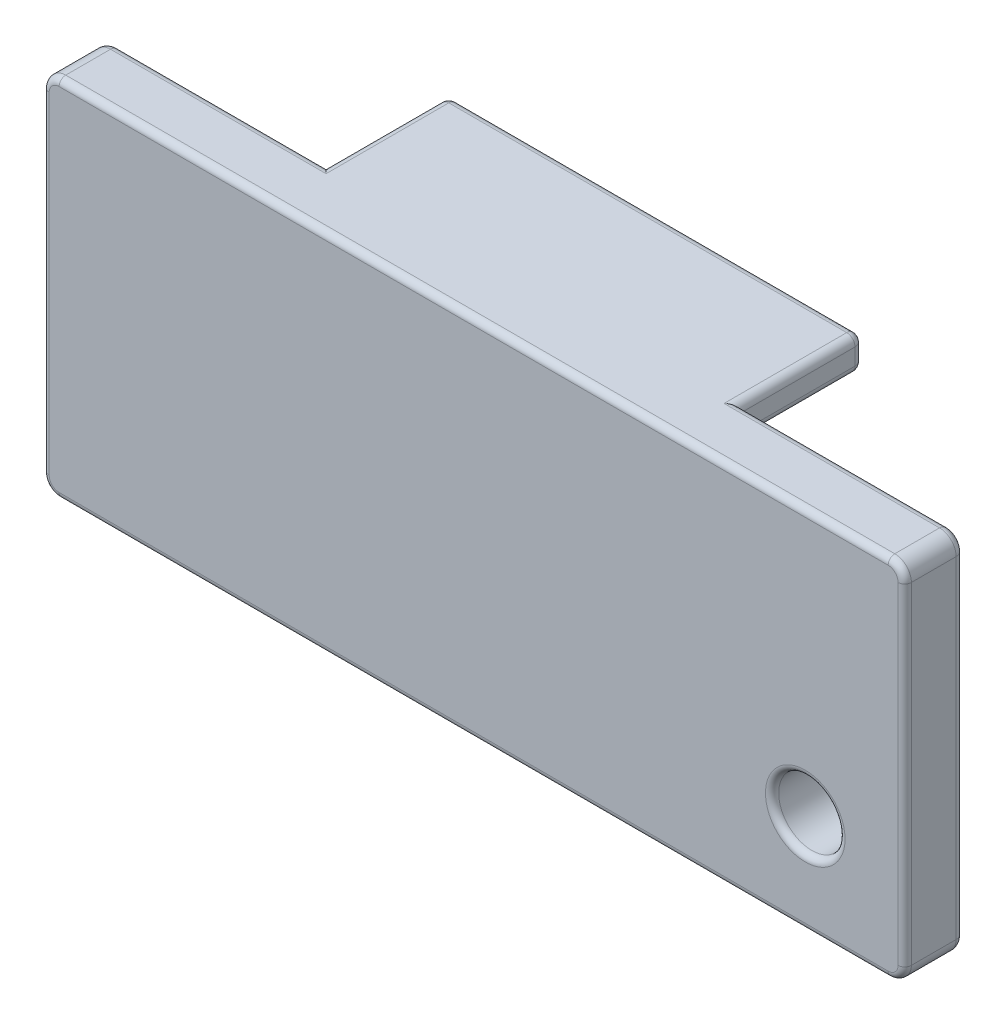
SolidWorks part; units mm, degrees
ref_plane "Front Plane" through (0, 0, 0) normal (0, 0, 1) x (1, 0, 0)
ref_plane "Top Plane" through (0, 0, 0) normal (0, 1, 0) x (1, 0, 0)
ref_plane "Right Plane" through (0, 0, 0) normal (1, 0, 0) x (0, 0, -1)
sketch "Sketch1" plane through (0, 0, 13.741) normal (0, 0, 1) x (1, 0, 0)
  line L0 (61.4432, -125.17) -> (87.4432, -125.17) construction
  line L1 (61.4432, -114.17) -> (61.4432, -125.17) construction
  line L2 (87.4432, -125.17) -> (87.4432, -114.17) construction
  line L3 (87.4432, -114.17) -> (61.4432, -114.17) construction
  line L4 (61.4432, -125.17) -> (87.4432, -125.17) construction
  line L5 (61.4432, -114.17) -> (61.4432, -125.17) construction
  line L6 (87.4432, -125.17) -> (87.4432, -114.17) construction
  line L7 (87.4432, -114.17) -> (61.4432, -114.17) construction
  line L8 (61.4432, -125.17) -> (87.4432, -125.17)
  line L9 (87.4432, -125.17) -> (87.4432, -114.17)
  line L10 (87.4432, -114.17) -> (61.4432, -114.17)
  line L11 (61.4432, -114.17) -> (61.4432, -125.17)
  dimension "D1" = 0
extrude "Boss-Extrude1" add sketch "Sketch1" against normal offset from surface (1.8 mm away) 0.2
fillet "Fillet1" radius 0.2 4 edges at (74.4432, -114.17, 13.741) (61.4432, -119.67, 13.741) (74.4432, -125.17, 13.741) (87.4432, -119.67, 13.741)
sketch "Sketch2" plane through (0, 0, 13.741) normal (0, 0, 1) x (1, 0, 0)
  line L0 (61.4432, -125.17) -> (87.4432, -125.17) construction
  line L1 (87.4432, -125.17) -> (87.4432, -114.17) construction
  circle A0 centre (84.4432, -122.17) radius 1
  dimension "D3" = 2
  dimension "D1" = 3
  dimension "D2" = 3
extrude "Cut-Extrude1" cut sketch "Sketch2" against normal through all
fillet "Fillet2" radius 0.5 8 edges at (61.4432, -125.17, 12.741) (61.4432, -114.17, 12.741) (87.4432, -114.17, 12.741) (87.4432, -125.17, 12.741) (87.3846, -125.1114, 13.6824) (87.3846, -114.2285, 13.6824) (61.5017, -114.2285, 13.6824) (61.5017, -125.1114, 13.6824)
fillet "Fillet3" radius 0.2 2 edges at (85.4432, -122.17, 11.941) (85.4432, -122.17, 13.741)
sketch "Sketch4" plane through (0, 0, 11.941) normal (0, 0, -1) x (-1, 0, 0)
  line L0 (-61.9432, -125.17) -> (-86.9432, -125.17) construction
  line L1 (-68.1932, -125.17) -> (-80.6932, -125.17)
  line L2 (-68.1932, -125.17) -> (-68.1932, -124.17)
  line L3 (-68.1932, -124.17) -> (-80.6932, -124.17)
  line L4 (-80.6932, -125.17) -> (-80.6932, -124.17)
  line L5 (-86.9432, -114.17) -> (-61.9432, -114.17) construction
  line L6 (-68.1932, -114.17) -> (-80.6932, -114.17)
  line L7 (-68.1932, -114.17) -> (-68.1932, -115.17)
  line L8 (-68.1932, -115.17) -> (-80.6932, -115.17)
  line L9 (-80.6932, -114.17) -> (-80.6932, -115.17)
  line L10 (-61.9432, -114.17) -> (-68.1932, -114.17)
  line L11 (-80.6932, -114.17) -> (-86.9432, -114.17)
  line M12 (-86.9432, -125.17) -> (-61.9432, -125.17)
  line M16 (-61.9432, -114.17) -> (-86.9432, -114.17)
  dimension "D1" = 12.5
  dimension "D2" = 1
  dimension "D3" = 1
extrude "Boss-Extrude2" add sketch "Sketch4" along normal offset from surface (3.7 mm away) 1 contours L4 L2 L3 M12 | L9 L8 L7 M16 region at (74.4432, -124.67, 11.941) region at (74.4432, -114.67, 11.941)
fillet "Fillet4" radius 0.25 14 edges at (65.0682, -114.17, 11.941) (61.5896, -114.3164, 11.941) (61.4432, -119.67, 11.941) (61.5896, -125.0235, 11.941) (83.8182, -125.17, 11.941) (87.2967, -125.0235, 11.941) (83.8182, -114.17, 11.941) (87.2967, -114.3164, 11.941) (74.4432, -114.17, 8.241) (74.4432, -115.17, 8.241) (74.4432, -124.17, 8.241) (74.4432, -125.17, 8.241) (65.0682, -125.17, 11.941) (87.4432, -119.67, 11.941)
fillet "Fillet5" radius 0.25 20 edges at (68.1932, -114.17, 10.341) (68.1932, -114.2432, 8.3142) (68.1932, -115.17, 10.216) (68.1932, -115.0967, 8.3142) (68.1932, -125.17, 10.341) (68.1932, -125.0967, 8.3142) (68.1932, -124.17, 10.216) (68.1932, -124.2432, 8.3142) (80.6932, -125.17, 10.341) (80.6932, -125.0967, 8.3142) (80.6932, -124.17, 10.216) (80.6932, -124.2432, 8.3142) (80.6932, -114.17, 10.341) (80.6932, -114.2432, 8.3142) (80.6932, -115.17, 10.216) (80.6932, -115.0967, 8.3142) (68.1932, -114.67, 8.241) (68.1932, -124.67, 8.241) (80.6932, -124.67, 8.241) (80.6932, -114.67, 8.241)
